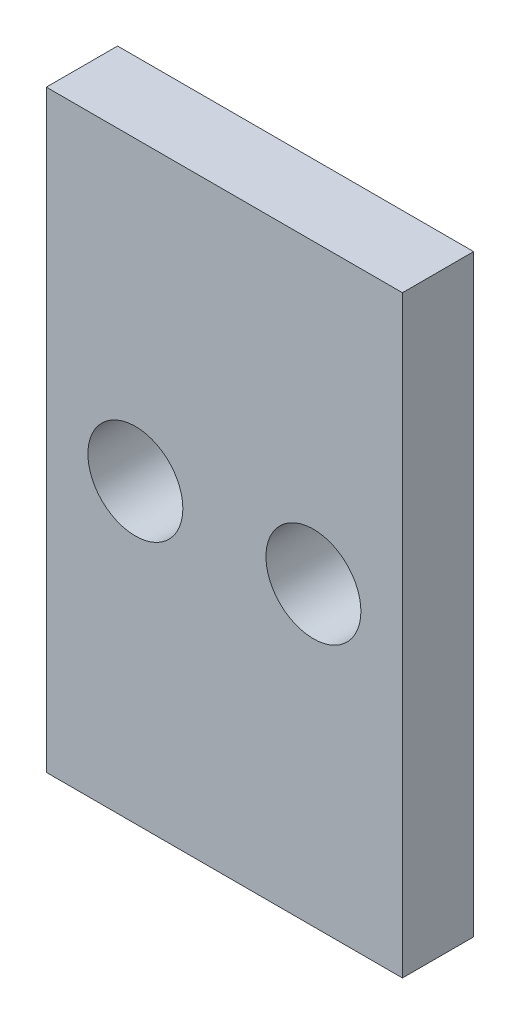
SolidWorks part; units mm, degrees
ref_plane "Płaszczyzna przednia" through (0, 0, 0) normal (0, 0, 1) x (1, 0, 0)
ref_plane "Płaszczyzna górna" through (0, 0, 0) normal (0, 1, 0) x (1, 0, 0)
ref_plane "Płaszczyzna prawa" through (0, 0, 0) normal (1, 0, 0) x (0, 0, -1)
sketch "Sketch1" plane through (0, 0, 0) normal (0, 0, 1) x (1, 0, 0)
  line L0 (0, 0) -> (26.9472, 0) construction
  line L1 (-15, 25) -> (15, 25)
  line L2 (-15, 25) -> (-15, -25)
  line L3 (-15, -25) -> (15, -25)
  line L4 (15, 25) -> (15, -25)
  line L5 (-15, 25) -> (15, -25) construction
  line L6 (-15, -25) -> (15, 25) construction
  line L7 (26.9472, 0) -> (-27.3648, 0) construction
  circle A0 centre (-7.5, 0) radius 4
  circle A1 centre (7.5, 0) radius 4
  point P0 (0, 0)
  dimension "D5" = 8
  dimension "D6" = 8
  dimension "D1" = 15
  dimension "D2" = 7.5
  dimension "D3" = 30
  dimension "D4" = 50
extrude "Boss-Extrude1" add sketch "Sketch1" along normal blind 6
